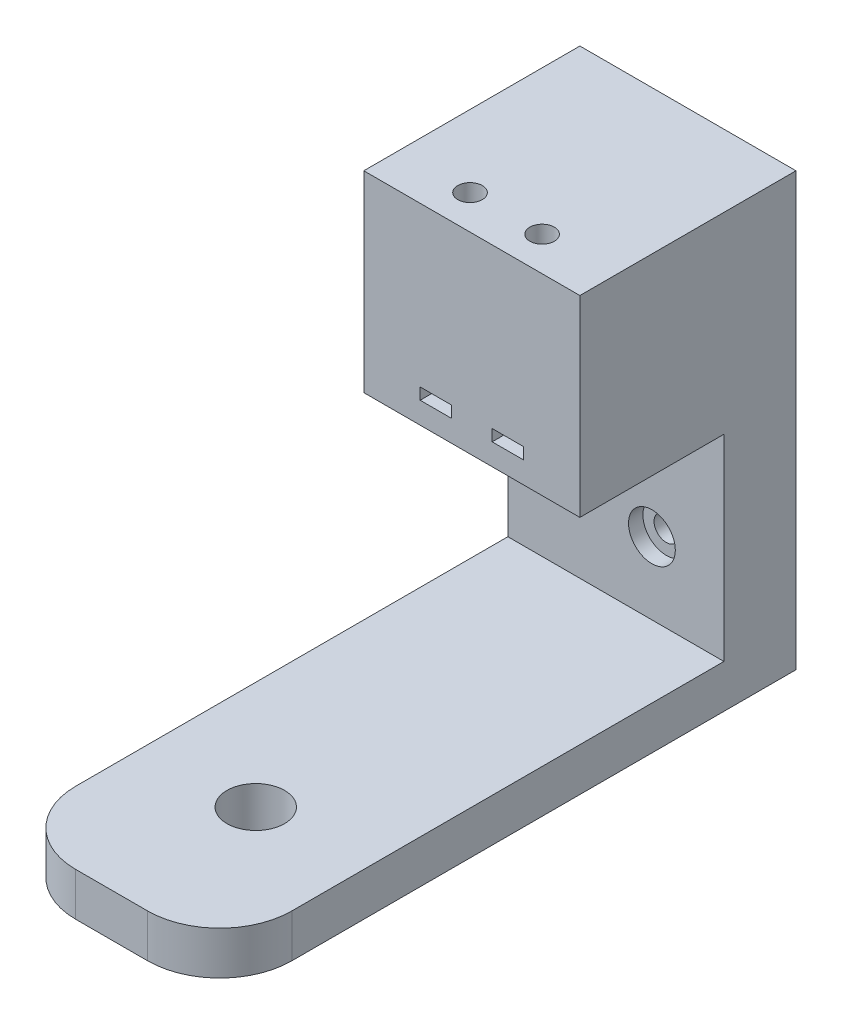
SolidWorks part; units mm, degrees
ref_plane "Plan de face" through (0, 0, 0) normal (0, 0, 1) x (1, 0, 0)
ref_plane "Plan de dessus" through (0, 0, 0) normal (0, 1, 0) x (1, 0, 0)
ref_plane "Plan de droite" through (0, 0, 0) normal (1, 0, 0) x (0, 0, -1)
sketch "Esquisse1" plane through (0, 0, 0) normal (0, 0, 1) x (1, 0, 0)
  line L1 (0, 0) -> (30, 0)
  line L2 (0, 0) -> (0, 60)
  line L3 (0, 60) -> (30, 60)
  line L4 (30, 0) -> (30, 60)
  dimension "D1" = 30
  dimension "D2" = 60
extrude "Boss.-Extru.1" add sketch "Esquisse1" along normal blind 10
sketch "Esquisse2" plane through (0, 0, 10) normal (0, 0, 1) x (1, 0, 0)
  line L0 (30, 0) -> (30, 60) construction
  line L1 (0, 0) -> (30, 0) construction
  line L2 (0, 60) -> (0, 0) construction
  line L3 (30, 0) -> (30, 6)
  line L4 (0, 0) -> (30, 0)
  line L5 (0, 6) -> (0, 0)
  line L6 (0, 6) -> (30, 6)
  dimension "D1" = 6
extrude "Boss.-Extru.2" add sketch "Esquisse2" along normal blind 70
sketch "Esquisse3" plane through (0, 0, 0) normal (0, -1, 0) x (1, 0, 0)
  line L0 (0, 80) -> (0, 0) construction
  line L1 (0, 0) -> (30, 0) construction
  circle A0 centre (15, 60) radius 4
  dimension "D3" = 8
  dimension "D1" = 15
  dimension "D2" = 60
extrude "Enlèv. mat.-Extru.1" cut sketch "Esquisse3" against normal up to surface (6 mm away) up to face at (15, 6, 45)
sketch "Esquisse4" plane through (0, 0, 10) normal (0, 0, 1) x (1, 0, 0)
  line L0 (30, 6) -> (30, 60) construction
  line L1 (30, 33.32) -> (30, 60)
  line L2 (0, 60) -> (0, 6) construction
  line L3 (30, 60) -> (0, 60) construction
  line L4 (0, 60) -> (0, 33.32)
  line L5 (30, 60) -> (0, 60)
  line L6 (0, 33.32) -> (30, 33.32)
  line L8 (30, 6) -> (0, 6) construction
  dimension "D1" = 27.32
extrude "Boss.-Extru.3" add sketch "Esquisse4" along normal blind 20
sketch "Esquisse5" plane through (0, 33.32, 0) normal (0, -1, 0) x (1, 0, 0)
  line L0 (0, 30) -> (0, 10) construction
  line L2 (0, 30) -> (30, 30) construction
  circle A0 centre (10, 25.25) radius 2.2
  circle A1 centre (20, 25.25) radius 2.2
  dimension "D3" = 4.4
  dimension "D4" = 4.4
  dimension "D1" = 10
  dimension "D2" = 10
  dimension "D5" = 4.75
  dimension "D6" = 4.75
hole_wizard "Dégagement M31" positions "Esquisse8" profile "Esquisse7" hole size "M3" standard "ISO"
sketch "Esquisse8" plane through (0, 33.32, 0) normal (0, -1, 0) x (-1, 0, 0)
  point P0 (-10, -25.25)
  point P3 (-20, -25.25)
sketch "Esquisse7" plane through (10, 33.32, 25.25) normal (1, 0, 0) x (0, 0, -1)
  line L0 (0, 0) -> (0, 27.7015)
  line L1 (0, 27.7015) -> (1.7, 26.68)
  line L2 (1.7, 26.68) -> (1.7, 0)
  line L5 (1.7, 0) -> (0, 0)
  line L10 (0, 27.7015) -> (-1.7, 26.68) construction
  line L11 (0, -6.35) -> (0, 107.95) construction
  dimension "Diamètre du perçage" = 3.4
  dimension "Profondeur du perçage" = 26.68
  dimension "Angle de pointe" = 118
sketch "Esquisse9" plane through (0, 0, 10) normal (0, 0, 1) x (1, 0, 0)
  line L0 (0, 33.32) -> (0, 6) construction
  line L1 (30, 6) -> (30, 33.32) construction
  line L2 (30, 6) -> (0, 6) construction
  line L3 (0, 33.32) -> (30, 33.32) construction
  circle A1 centre (20, 16) radius 1.5
  circle A2 centre (10, 23.32) radius 1.5
  dimension "D2" = 3
  dimension "D4" = 3
  dimension "D1" = 10
  dimension "D3" = 10
  dimension "D5" = 10
  dimension "D6" = 10
hole_wizard "Chambrage pour tête cylindrique fendue M31" positions "Esquisse10" profile "Esquisse12" counterbore size "M3" standard "ISO"
sketch "Esquisse10" plane through (0, 0, 10) normal (0, 0, 1) x (1, 0, 0)
  point P0 (10, 23.32)
  point P3 (20, 16)
sketch "Esquisse12" plane through (10, 23.32, 10) normal (1, 0, 0) x (0, -1, 0)
  line L0 (0, 0) -> (0, 11.0215)
  line L1 (0, 11.0215) -> (1.7, 10)
  line L2 (1.7, 10) -> (1.7, 2)
  line L3 (1.7, 2) -> (3.25, 2)
  line L4 (3.25, 2) -> (3.25, 0)
  line L5 (3.25, 0) -> (0, 0)
  line L10 (0, 11.0215) -> (-1.7, 10) construction
  line L11 (0, -6.35) -> (0, 107.95) construction
  dimension "Diamètre du perçage" = 3.4
  dimension "Profondeur du perçage" = 10
  dimension "Diamètre du chambrage" = 6.5
  dimension "Profondeur du chambrage" = 2
  dimension "Angle de pointe" = 118
fillet "Congé1" radius 10 2 edges at (30, 3, 80) (0, 3, 80)
sketch "Esquisse13" plane through (0, 0, 30) normal (0, 0, 1) x (1, 0, 0)
  line L0 (0, 33.32) -> (30, 33.32) construction
  line L1 (7.825, 37.92) -> (12.175, 37.92)
  line L2 (7.825, 37.92) -> (7.825, 36.32)
  line L3 (7.825, 36.32) -> (12.175, 36.32)
  line L4 (12.175, 37.92) -> (12.175, 36.32)
  line L5 (22.175, 37.92) -> (17.825, 37.92)
  line L6 (22.175, 37.92) -> (22.175, 36.32)
  line L7 (22.175, 36.32) -> (17.825, 36.32)
  line L8 (17.825, 37.92) -> (17.825, 36.32)
  line L9 (0, 60) -> (0, 33.32) construction
  line L10 (30, 33.32) -> (30, 60) construction
  point P10 (10, 37.92)
  point P13 (20, 37.92)
  point P16 (11.9788, 38.3735)
  dimension "D1" = 3
  dimension "D2" = 3
  dimension "D3" = 10
  dimension "D4" = 10
  dimension "D5" = 4.35
  dimension "D6" = 4.35
  dimension "D7" = 1.6
  dimension "D8" = 1.6
extrude "Enlèv. mat.-Extru.2" cut sketch "Esquisse13" against normal blind 8.11
equation "\"D4@Esquisse5\"=\"D3@Esquisse5\""
equation "\"D6@Esquisse5\"=\"D5@Esquisse5\""
